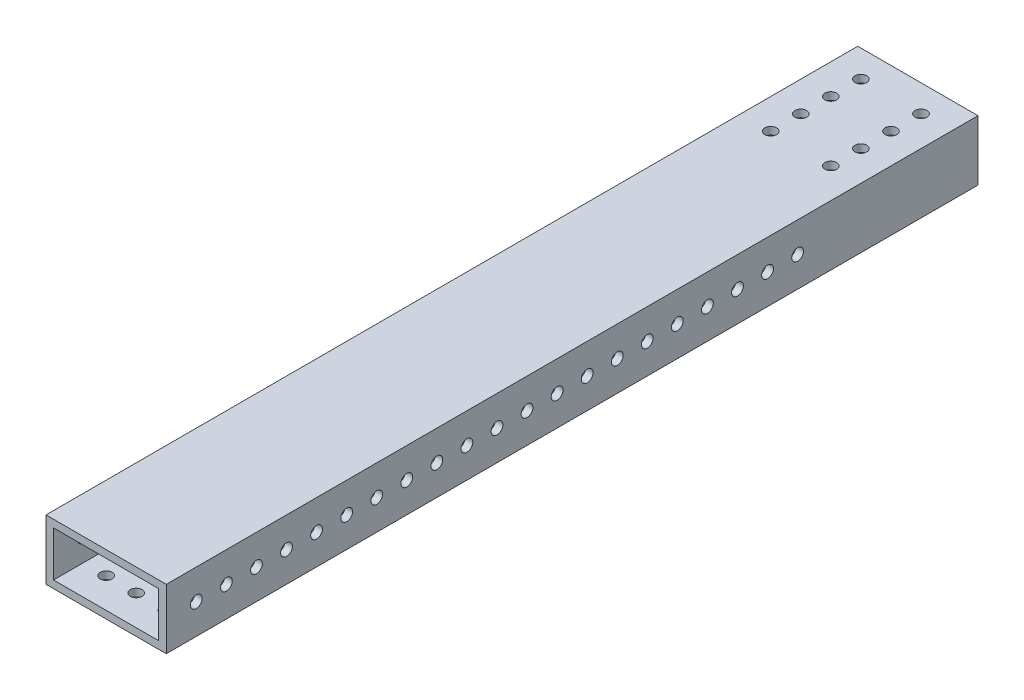
SolidWorks part; units mm, degrees
material "6061-T6 (SS)"
ref_plane "Front Plane" through (0, 0, 0) normal (0, 0, 1) x (1, 0, 0)
ref_plane "Top Plane" through (0, 0, 0) normal (0, 1, 0) x (1, 0, 0)
ref_plane "Right Plane" through (0, 0, 0) normal (1, 0, 0) x (0, 0, -1)
sketch "Sketch1" plane through (0, 0, 0) normal (0, 1, 0) x (1, 0, 0)
  line L1 (0, 0) -> (50.8, 0)
  line L2 (0, 0) -> (0, 342.9)
  line L3 (0, 342.9) -> (50.8, 342.9)
  line L4 (50.8, 0) -> (50.8, 342.9)
  dimension "D1" = 50.8
  dimension "D2" = 342.9
extrude "Boss-Extrude1" add sketch "Sketch1" along normal blind 25.4
shell "Shell1" thickness 3.175 removed face at (25.4, 12.7, -342.9) removed face at (25.4, 12.7, 0)
sketch "Sketch2" plane through (0, 0, 0) normal (-1, 0, 0) x (0, 0, 1)
  line L0 (0, 12.7) -> (-342.9, 12.7) construction
  line L1 (0, 25.4) -> (0, 0) construction
  line L2 (-342.9, 25.4) -> (-342.9, 0) construction
  circle A0 centre (-12.7, 12.7) radius 2.4892
  circle A1 centre (-25.4, 12.7) radius 2.4892
  circle A2 centre (-38.1, 12.7) radius 2.4892
  circle A3 centre (-50.8, 12.7) radius 2.4892
  circle A4 centre (-63.5, 12.7) radius 2.4892
  circle A5 centre (-76.2, 12.7) radius 2.4892
  circle A6 centre (-88.9, 12.7) radius 2.4892
  circle A7 centre (-101.6, 12.7) radius 2.4892
  circle A8 centre (-114.3, 12.7) radius 2.4892
  circle A9 centre (-127, 12.7) radius 2.4892
  circle A10 centre (-139.7, 12.7) radius 2.4892
  circle A11 centre (-152.4, 12.7) radius 2.4892
  circle A12 centre (-165.1, 12.7) radius 2.4892
  circle A13 centre (-177.8, 12.7) radius 2.4892
  circle A14 centre (-190.5, 12.7) radius 2.4892
  circle A15 centre (-203.2, 12.7) radius 2.4892
  circle A16 centre (-215.9, 12.7) radius 2.4892
  circle A17 centre (-228.6, 12.7) radius 2.4892
  circle A18 centre (-241.3, 12.7) radius 2.4892
  circle A19 centre (-254, 12.7) radius 2.4892
  circle A20 centre (-266.7, 12.7) radius 2.4892
  dimension "D1" = 4.9784
  dimension "D2" = 12.7
  dimension "D3" = 12.7
  dimension "D4" = 21
extrude "Cut-Extrude1" cut sketch "Sketch2" against normal through all
sketch "Sketch3" plane through (0, 0, 0) normal (0, 1, 0) x (1, 0, 0)
  circle A0 centre (12.7, 293.4246) radius 2.4892 construction
  circle A1 centre (38.1, 293.4246) radius 2.4892 construction
  circle A2 centre (38.1, 306.1246) radius 2.4892 construction
  circle A3 centre (12.7, 306.1246) radius 2.4892 construction
  circle A4 centre (12.7, 318.8246) radius 2.4892 construction
  circle A5 centre (38.1, 318.8246) radius 2.4892 construction
  circle A6 centre (38.1, 331.5246) radius 2.4892 construction
  circle A7 centre (12.7, 331.5246) radius 2.4892 construction
  circle A8 centre (12.7, 293.4246) radius 2.4892
  circle A9 centre (38.1, 293.4246) radius 2.4892
  circle A10 centre (38.1, 306.1246) radius 2.4892
  circle A11 centre (12.7, 306.1246) radius 2.4892
  circle A12 centre (12.7, 318.8246) radius 2.4892
  circle A13 centre (38.1, 318.8246) radius 2.4892
  circle A14 centre (38.1, 331.5246) radius 2.4892
  circle A15 centre (12.7, 331.5246) radius 2.4892
  circle A16 centre (38.1, 63.5) radius 2.4892 construction
  circle A17 centre (25.4, 63.5) radius 2.4892 construction
  circle A18 centre (12.7, 63.5) radius 2.4892 construction
  circle A19 centre (12.7, 50.8) radius 2.4892 construction
  circle A20 centre (25.4, 50.8) radius 2.4892 construction
  circle A21 centre (38.1, 50.8) radius 2.4892 construction
  circle A22 centre (12.7, 38.1) radius 2.4892 construction
  circle A23 centre (25.4, 38.1) radius 2.4892 construction
  circle A24 centre (38.1, 38.1) radius 2.4892 construction
  circle A25 centre (38.1, 25.4) radius 2.4892 construction
  circle A26 centre (25.4, 25.4) radius 2.4892 construction
  circle A27 centre (12.7, 25.4) radius 2.4892 construction
  circle A28 centre (12.7, 12.7) radius 2.4892 construction
  circle A29 centre (25.4, 12.7) radius 2.4892 construction
  circle A30 centre (38.1, 12.7) radius 2.4892 construction
  circle A31 centre (38.1, 63.5) radius 2.4892
  circle A32 centre (25.4, 63.5) radius 2.4892
  circle A33 centre (12.7, 63.5) radius 2.4892
  circle A34 centre (12.7, 50.8) radius 2.4892
  circle A35 centre (25.4, 50.8) radius 2.4892
  circle A36 centre (38.1, 50.8) radius 2.4892
  circle A37 centre (12.7, 38.1) radius 2.4892
  circle A38 centre (25.4, 38.1) radius 2.4892
  circle A39 centre (38.1, 38.1) radius 2.4892
  circle A40 centre (38.1, 25.4) radius 2.4892
  circle A41 centre (25.4, 25.4) radius 2.4892
  circle A42 centre (12.7, 25.4) radius 2.4892
  circle A43 centre (12.7, 12.7) radius 2.4892
  circle A44 centre (25.4, 12.7) radius 2.4892
  circle A45 centre (38.1, 12.7) radius 2.4892
extrude "Cut-Extrude2" cut sketch "Sketch3" along normal through all contours A14 | A15 | A13 | A12 | A11 | A10 | A9 | A8 region at (12.7, 0, -293.4246) region at (38.1, 0, -293.4246) region at (38.1, 0, -306.1246) region at (12.7, 0, -306.1246) region at (12.7, 0, -318.8246) region at (38.1, 0, -318.8246) region at (38.1, 0, -331.5246) region at (12.7, 0, -331.5246)
extrude "Cut-Extrude3" cut sketch "Sketch3<3>" along normal up to next contours A31 | A32 | A33 | A34 | A35 | A36 | A39 | A38 | A37 | A40 | A41 | A42 | A43 | A44 | A45 region at (38.1, 0, -63.5) region at (25.4, 0, -63.5) region at (12.7, 0, -63.5) region at (12.7, 0, -50.8) region at (25.4, 0, -50.8) region at (38.1, 0, -50.8) region at (12.7, 0, -38.1) region at (25.4, 0, -38.1) region at (38.1, 0, -38.1) region at (38.1, 0, -25.4) region at (25.4, 0, -25.4) region at (12.7, 0, -25.4) region at (12.7, 0, -12.7) region at (25.4, 0, -12.7) region at (38.1, 0, -12.7)
sketch "Sketch3<3>" plane through (0, 0, 0) normal (0, 1, 0) x (1, 0, 0) same geometry as "Sketch3"
